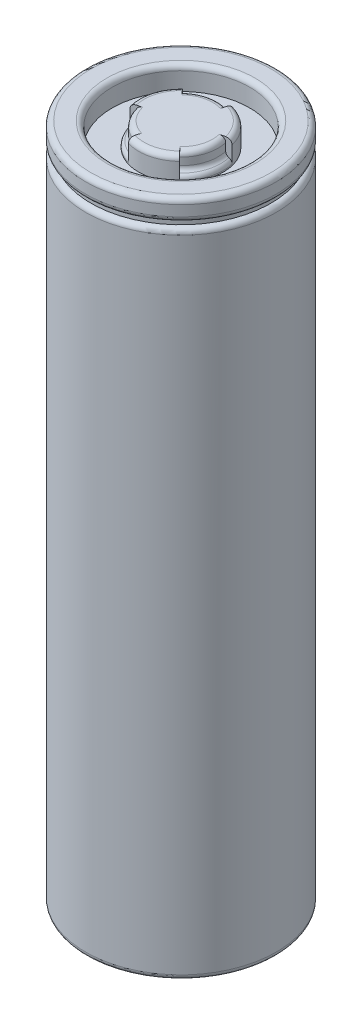
SolidWorks part; units mm, degrees
ref_plane "Alzado" through (0, 0, 0) normal (0, 0, 1) x (1, 0, 0)
ref_plane "Planta" through (0, 0, 0) normal (0, 1, 0) x (1, 0, 0)
ref_plane "Vista lateral" through (0, 0, 0) normal (1, 0, 0) x (0, 0, -1)
sketch "Sketch2" plane through (0, 0, 0) normal (0, 0, 1) x (1, 0, 0)
  line L0 (-12.1424, -5.6897) -> (-12.1424, 58.3103)
  line L1 (-12.1424, 58.3103) -> (-3.1424, 58.3103)
  line L2 (-3.1424, 58.3103) -> (-3.1424, 56.3103)
  line L3 (-3.1424, 56.3103) -> (-3.6424, 56.3103)
  line L4 (-3.6424, 56.3103) -> (-3.6424, 55.8103)
  line L5 (-3.6424, 55.8103) -> (-3.1424, 55.8103)
  line L6 (-3.1424, 55.8103) -> (-3.1424, -5.6897)
  line L7 (-3.1424, -5.6897) -> (-12.1424, -5.6897)
  dimension "D1" = 2
  dimension "D2" = 0.5
  dimension "D3" = 0.5
  dimension "D4" = 9
  dimension "D5" = 9
  dimension "D6" = 64
revolve "Revolve1" add sketch "Sketch2" angle 360 about L0
fillet "Fillet1" radius 0.5 1 edges at (-12.1424, -5.6897, -9)
fillet "Fillet2" radius 0.5 2 edges at (-12.1424, 55.8103, -9) (-12.1424, 56.3103, -9)
sketch "Sketch3" plane through (0, 58.3103, 0) normal (0, 1, 0) x (1, 0, 0)
  circle A0 centre (-12.1424, 0) radius 6.5
  circle A1 centre (-12.1424, 0) radius 9 construction
  dimension "D1" = 13
extrude "Cut-Extrude1" cut sketch "Sketch3" against normal blind 2.2
sketch "Sketch4" plane through (0, 56.1103, 0) normal (0, 1, 0) x (1, 0, 0)
  circle A0 centre (-12.1424, 0) radius 4
  circle A1 centre (-12.1424, 0) radius 6.5 construction
  dimension "D1" = 8
extrude "Boss-Extrude1" add sketch "Sketch4" along normal up to surface (2.2 mm away) up to face at (-12.1424, 58.3103, 6.5)
fillet "Fillet3" radius 0.5 2 edges at (-12.1424, 58.3103, -9) (-12.1424, 58.3103, 6.5)
ref_plane "Plane1" through (0, 58.8103, 0) normal (0, 1, 0) x (1, 0, 0)
sketch "Sketch6" plane through (0, 58.8103, 0) normal (0, 1, 0) x (1, 0, 0)
  line L0 (-8.7405, 0.8229) -> (-8.2545, 0.9404)
  line L1 (-9.7289, -2.5347) -> (-9.3841, -2.8968)
  circle A0 centre (-12.1424, 0) radius 3.5
  circle A1 centre (-12.1424, 0) radius 4 construction
  circle A2 centre (-12.1424, 0) radius 4 construction
  arc A3 (-8.2545, 0.9404) -> (-9.3841, -2.8968) centre (-12.1424, 0) cw
  dimension "D1" = 7
  dimension "D2" = 60
extrude "Cut-Extrude3" cut sketch "Sketch6" against normal blind 2.2 contours A3 L0 A0 L1 region at (-8.7021, 58.8103, 1.0127)
pattern_circular "CirPattern1" count 3 over 360 about axis through (-12.1424, 58.3103, 0) along (0, 1, 0) of "Cut-Extrude3"
fillet "Fillet4" radius 0.5 6 edges at (-12.9653, 58.3103, -3.4019) (-9.2456, 58.3103, -2.7584) (-8.7849, 58.3103, 0.9883) (-11.202, 58.3103, 3.8879) (-14.6771, 58.3103, 2.4136) (-15.9796, 58.3103, -1.1295)
fillet "Fillet5" radius 0.5 3 edges at (-12.9653, 56.6103, -3.4019) (-8.7849, 56.6103, 0.9883) (-14.6771, 56.6103, 2.4136)
fillet "Fillet6" radius 0.5 3 edges at (-8.3052, 56.6103, 1.1295) (-15.0392, 56.6103, 2.7584) (-13.0828, 56.6103, -3.8879)
